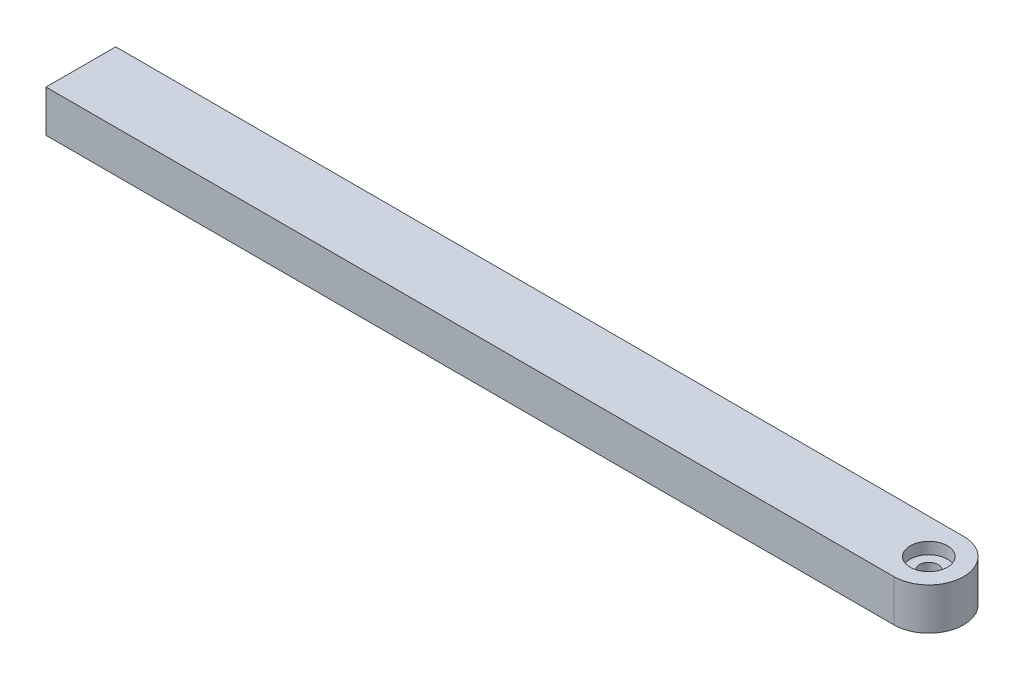
SolidWorks part; units mm, degrees
ref_plane "Front Plane" through (0, 0, 0) normal (0, 0, 1) x (1, 0, 0)
ref_plane "Top Plane" through (0, 0, 0) normal (0, 1, 0) x (1, 0, 0)
ref_plane "Right Plane" through (0, 0, 0) normal (1, 0, 0) x (0, 0, -1)
sketch "Sketch1" plane through (0, 0, 0) normal (0, 1, 0) x (1, 0, 0)
  line L0 (197.8548, 0) -> (177.8548, 0) construction
  line L2 (-187.1452, 15) -> (-187.1452, -15)
  line L5 (0, -15) -> (0, 15) construction
  line L7 (-187.1452, 15) -> (177.8548, 15)
  line L8 (-187.1452, -15) -> (177.8548, -15)
  line L9 (192.8548, 0) -> (-187.1452, 0) construction
  circle A0 centre (177.8548, 0) radius 4
  arc A1 (177.8548, 15) -> (177.8548, -15) centre (177.8548, 0) cw
  point P0 (0, 0)
  dimension "D4" = 8
  dimension "D1" = 30
  dimension "D2" = 380
  dimension "D3" = 20
extrude "Boss-Extrude1" add sketch "Sketch1" along normal blind 18
sketch "Sketch2" plane through (0, 18, 0) normal (0, 1, 0) x (1, 0, 0)
  circle A0 centre (177.8548, 0) radius 8
  dimension "D1" = 16
extrude "Cut-Extrude1" cut sketch "Sketch2" against normal blind 5
